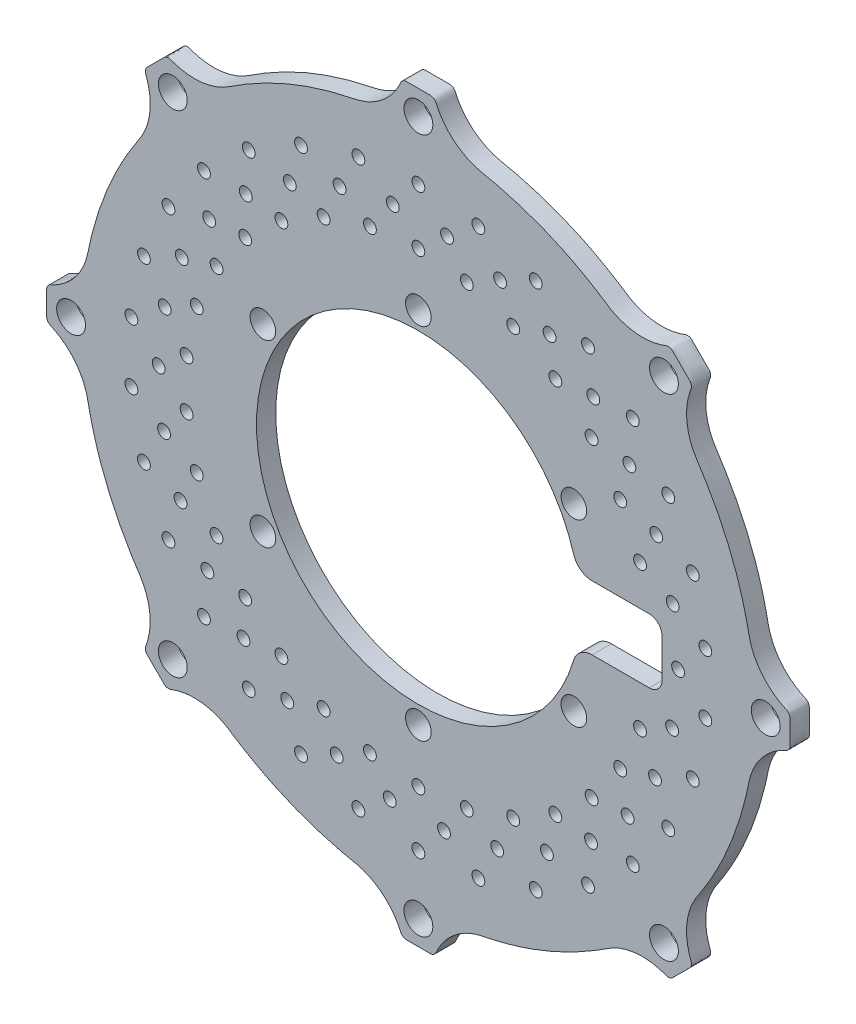
SolidWorks part; units mm, degrees
material "7075-T6, Plate (SS)"
ref_plane "Front Plane" through (0, 0, 0) normal (0, 0, 1) x (1, 0, 0)
ref_plane "Top Plane" through (0, 0, 0) normal (0, 1, 0) x (1, 0, 0)
ref_plane "Right Plane" through (0, 0, 0) normal (1, 0, 0) x (0, 0, -1)
sketch "Sketch1" plane through (0, 0, 0) normal (0, 0, 1) x (1, 0, 0)
  line L1 (-3.9972, 40.3023) -> (0, 28) construction
  line L3 (38, -3) -> (38, 3) construction
  line L4 (38, -3) -> (38, 3)
  line L5 (36, 5) -> (27.0936, 5)
  line L6 (36, -5) -> (27.0936, -5)
  line L7 (0, 0) -> (0, 48) construction
  line L8 (-2.8952, 57.0706) -> (-2.7624, 57.363)
  line L9 (-1.8466, 57.9614) -> (1.8466, 57.9614) construction
  line L10 (2.7624, 57.363) -> (2.7753, 57.3336)
  line L11 (-5, 52.2614) -> (5, 52.2614) construction
  line L12 (39.6791, 42.2906) -> (42.2906, 39.6791) construction
  line L13 (38.5785, 42.5034) -> (38.6085, 42.5151) construction
  line L14 (42.5151, 38.6085) -> (42.5034, 38.5785) construction
  line L15 (57.9614, 1.8466) -> (57.9614, -1.8466) construction
  line L16 (57.3336, 2.7753) -> (57.363, 2.7624) construction
  line L17 (57.363, -2.7624) -> (57.3336, -2.7753) construction
  line L18 (42.2906, -39.6791) -> (39.6791, -42.2906) construction
  line L19 (42.5034, -38.5785) -> (42.5151, -38.6085) construction
  line L20 (38.6085, -42.5151) -> (38.5785, -42.5034) construction
  line L21 (1.8466, -57.9614) -> (-1.8466, -57.9614) construction
  line L22 (2.7753, -57.3336) -> (2.7624, -57.363) construction
  line L23 (-2.7624, -57.363) -> (-2.7753, -57.3336) construction
  line L24 (-39.6791, -42.2906) -> (-42.2906, -39.6791) construction
  line L25 (-38.5785, -42.5034) -> (-38.6085, -42.5151) construction
  line L26 (-42.5151, -38.6085) -> (-42.5034, -38.5785) construction
  line L27 (-57.9614, -1.8466) -> (-57.9614, 1.8466) construction
  line L28 (-57.3336, -2.7753) -> (-57.363, -2.7624) construction
  line L29 (-57.363, 2.7624) -> (-57.3336, 2.7753) construction
  line L30 (-42.2906, 39.6791) -> (-39.6791, 42.2906) construction
  line L31 (-42.5034, 38.5785) -> (-42.5151, 38.6085) construction
  line L32 (-38.6085, 42.5151) -> (-38.5785, 42.5034) construction
  arc A0 (-10.0239, 51.5342) -> (-29.3522, 43.5281) centre (0, 0) ccw construction
  circle A1 centre (0, 0) radius 28 construction
  arc A3 (24.2164, 7.1504) -> (24.2164, -7.1504) centre (0, 0) ccw
  arc A4 (38, 3) -> (34, 3) centre (36, 3) ccw construction
  arc A5 (34, -3) -> (38, -3) centre (36, -3) ccw construction
  arc A6 (36, -5) -> (38, -3) centre (36, -3) ccw
  arc A7 (38, 3) -> (36, 5) centre (36, 3) ccw
  arc A8 (27.0936, -5) -> (24.2164, -7.1504) centre (27.0936, -8) ccw
  arc A9 (27.0936, 5) -> (24.2164, 7.1504) centre (27.0936, 8) cw
  circle A10 centre (0, 0) radius 36.3456 construction
  circle A11 centre (0, 36.3456) radius 1
  circle A12 centre (0, 45) radius 1
  arc A13 (45, 0) -> (-45, 0) centre (0, 0) ccw construction
  circle A14 centre (9.356, 44.0166) radius 1
  circle A15 centre (7.5567, 35.5513) radius 1
  circle A16 centre (18.3031, 41.1095) radius 1
  circle A17 centre (14.7831, 33.2033) radius 1
  circle A18 centre (26.4503, 36.4058) radius 1
  circle A19 centre (21.3634, 29.4042) radius 1
  circle A20 centre (33.4415, 30.1109) radius 1
  circle A21 centre (27.01, 24.3199) radius 1
  circle A22 centre (38.9711, 22.5) radius 1
  circle A23 centre (31.4762, 18.1728) radius 1
  circle A24 centre (42.7975, 13.9058) radius 1
  circle A25 centre (34.5667, 11.2314) radius 1
  circle A26 centre (44.7535, 4.7038) radius 1
  circle A27 centre (36.1465, 3.7991) radius 1
  circle A28 centre (44.7535, -4.7038) radius 1
  circle A29 centre (36.1465, -3.7991) radius 1
  circle A30 centre (42.7975, -13.9058) radius 1
  circle A31 centre (34.5667, -11.2314) radius 1
  circle A32 centre (38.9711, -22.5) radius 1
  circle A33 centre (31.4762, -18.1728) radius 1
  circle A34 centre (33.4415, -30.1109) radius 1
  circle A35 centre (27.01, -24.3199) radius 1
  circle A36 centre (26.4503, -36.4058) radius 1
  circle A37 centre (21.3634, -29.4042) radius 1
  circle A38 centre (18.3031, -41.1095) radius 1
  circle A39 centre (14.7831, -33.2033) radius 1
  circle A40 centre (9.356, -44.0166) radius 1
  circle A41 centre (7.5567, -35.5513) radius 1
  circle A42 centre (0, -45) radius 1
  circle A43 centre (0, -36.3456) radius 1
  circle A44 centre (-9.356, -44.0166) radius 1
  circle A45 centre (-7.5567, -35.5513) radius 1
  circle A46 centre (-18.3031, -41.1095) radius 1
  circle A47 centre (-14.7831, -33.2033) radius 1
  circle A48 centre (-26.4503, -36.4058) radius 1
  circle A49 centre (-21.3634, -29.4042) radius 1
  circle A50 centre (-33.4415, -30.1109) radius 1
  circle A51 centre (-27.01, -24.3199) radius 1
  circle A52 centre (-38.9711, -22.5) radius 1
  circle A53 centre (-31.4762, -18.1728) radius 1
  circle A54 centre (-42.7975, -13.9058) radius 1
  circle A55 centre (-34.5667, -11.2314) radius 1
  circle A56 centre (-44.7535, -4.7038) radius 1
  circle A57 centre (-36.1465, -3.7991) radius 1
  circle A58 centre (-44.7535, 4.7038) radius 1
  circle A59 centre (-36.1465, 3.7991) radius 1
  circle A60 centre (-42.7975, 13.9058) radius 1
  circle A61 centre (-34.5667, 11.2314) radius 1
  circle A62 centre (-38.9711, 22.5) radius 1
  circle A63 centre (-31.4762, 18.1728) radius 1
  circle A64 centre (-33.4415, 30.1109) radius 1
  circle A65 centre (-27.01, 24.3199) radius 1
  circle A66 centre (-26.4503, 36.4058) radius 1
  circle A67 centre (-21.3634, 29.4042) radius 1
  circle A68 centre (-18.3031, 41.1095) radius 1
  circle A69 centre (-14.7831, 33.2033) radius 1
  circle A70 centre (-9.356, 44.0166) radius 1
  circle A71 centre (-7.5567, 35.5513) radius 1
  circle A72 centre (0, 0) radius 40.5 construction
  circle A73 centre (-3.9972, 40.3023) radius 1
  circle A74 centre (4.4694, 40.2526) radius 1
  circle A75 centre (12.7407, 38.4438) radius 1
  circle A76 centre (20.4552, 34.9547) radius 1
  circle A77 centre (27.2757, 29.938) radius 1
  circle A78 centre (32.9042, 23.6128) radius 1
  circle A79 centre (37.0945, 16.2557) radius 1
  circle A80 centre (39.6637, 8.1881) radius 1
  circle A81 centre (40.4993, -0.2374) radius 1
  circle A82 centre (39.5649, -8.6525) radius 1
  circle A83 centre (36.9014, -16.6894) radius 1
  circle A84 centre (32.6251, -23.9969) radius 1
  circle A85 centre (26.9229, -30.2557) radius 1
  circle A86 centre (20.0441, -35.1921) radius 1
  circle A87 centre (12.2892, -38.5905) radius 1
  circle A88 centre (3.9972, -40.3023) radius 1
  circle A89 centre (-4.4694, -40.2526) radius 1
  circle A90 centre (-12.7407, -38.4438) radius 1
  circle A91 centre (-20.4552, -34.9547) radius 1
  circle A92 centre (-27.2757, -29.938) radius 1
  circle A93 centre (-32.9042, -23.6128) radius 1
  circle A94 centre (-37.0945, -16.2557) radius 1
  circle A95 centre (-39.6637, -8.1881) radius 1
  circle A96 centre (-40.4993, 0.2374) radius 1
  circle A97 centre (-39.5649, 8.6525) radius 1
  circle A98 centre (-36.9014, 16.6894) radius 1
  circle A99 centre (-32.6251, 23.9969) radius 1
  circle A100 centre (-26.9229, 30.2557) radius 1
  circle A101 centre (-20.0441, 35.1921) radius 1
  circle A102 centre (-12.2892, 38.5905) radius 1
  arc A104 (-2.8952, 57.0706) -> (-10.0239, 51.5342) centre (-11.9332, 61.3502) cw construction
  arc A105 (2.7753, 57.3336) -> (10.0239, 51.5342) centre (11.9332, 61.3502) ccw construction
  arc A106 (38.5785, 42.5034) -> (29.3522, 43.5281) centre (34.9431, 51.8192) cw construction
  arc A107 (42.5034, 38.5785) -> (43.5281, 29.3522) centre (51.8192, 34.9431) ccw construction
  arc A108 (57.3336, 2.7753) -> (51.5342, 10.0239) centre (61.3502, 11.9332) cw construction
  arc A109 (57.3336, -2.7753) -> (51.5342, -10.0239) centre (61.3502, -11.9332) ccw construction
  arc A110 (42.5034, -38.5785) -> (43.5281, -29.3522) centre (51.8192, -34.9431) cw construction
  arc A111 (38.5785, -42.5034) -> (29.3522, -43.5281) centre (34.9431, -51.8192) ccw construction
  arc A112 (2.7753, -57.3336) -> (10.0239, -51.5342) centre (11.9332, -61.3502) cw construction
  arc A113 (-2.7753, -57.3336) -> (-10.0239, -51.5342) centre (-11.9332, -61.3502) ccw construction
  arc A114 (-38.5785, -42.5034) -> (-29.3522, -43.5281) centre (-34.9431, -51.8192) cw construction
  arc A115 (-42.5034, -38.5785) -> (-43.5281, -29.3522) centre (-51.8192, -34.9431) ccw construction
  arc A116 (-57.3336, -2.7753) -> (-51.5342, -10.0239) centre (-61.3502, -11.9332) cw construction
  arc A117 (-57.3336, 2.7753) -> (-51.5342, 10.0239) centre (-61.3502, 11.9332) ccw construction
  arc A118 (-42.5034, 38.5785) -> (-43.5281, 29.3522) centre (-51.8192, 34.9431) cw construction
  arc A119 (-38.5785, 42.5034) -> (-29.3522, 43.5281) centre (-34.9431, 51.8192) ccw construction
  arc A120 (29.3522, 43.5281) -> (10.0239, 51.5342) centre (0, 0) ccw construction
  arc A121 (51.5342, 10.0239) -> (43.5281, 29.3522) centre (0, 0) ccw construction
  arc A122 (10.0239, -51.5342) -> (29.3522, -43.5281) centre (0, 0) ccw construction
  arc A123 (43.5281, -29.3522) -> (51.5342, -10.0239) centre (0, 0) ccw construction
  arc A124 (-29.3522, -43.5281) -> (-10.0239, -51.5342) centre (0, 0) ccw construction
  arc A125 (-51.5342, -10.0239) -> (-43.5281, -29.3522) centre (0, 0) ccw construction
  arc A126 (-43.5281, 29.3522) -> (-51.5342, 10.0239) centre (0, 0) ccw construction
  arc A127 (1.8466, 57.9614) -> (2.7624, 57.363) centre (1.8466, 56.9614) cw construction
  arc A128 (-2.7624, 57.363) -> (-1.8466, 57.9614) centre (-1.8466, 56.9614) cw construction
  arc A129 (-42.2906, 39.6791) -> (-42.5151, 38.6085) centre (-41.5835, 38.972) ccw construction
  arc A130 (-39.6791, 42.2906) -> (-38.6085, 42.5151) centre (-38.972, 41.5835) cw construction
  arc A131 (-57.9614, 1.8466) -> (-57.363, 2.7624) centre (-56.9614, 1.8466) cw construction
  arc A132 (-57.9614, -1.8466) -> (-57.363, -2.7624) centre (-56.9614, -1.8466) ccw construction
  arc A133 (-42.2906, -39.6791) -> (-42.5151, -38.6085) centre (-41.5835, -38.972) cw construction
  arc A134 (-39.6791, -42.2906) -> (-38.6085, -42.5151) centre (-38.972, -41.5835) ccw construction
  arc A135 (-1.8466, -57.9614) -> (-2.7624, -57.363) centre (-1.8466, -56.9614) cw construction
  arc A136 (1.8466, -57.9614) -> (2.7624, -57.363) centre (1.8466, -56.9614) ccw construction
  arc A137 (42.2906, -39.6791) -> (42.5151, -38.6085) centre (41.5835, -38.972) ccw construction
  arc A138 (39.6791, -42.2906) -> (38.6085, -42.5151) centre (38.972, -41.5835) cw construction
  arc A139 (57.9614, -1.8466) -> (57.363, -2.7624) centre (56.9614, -1.8466) cw construction
  arc A140 (57.9614, 1.8466) -> (57.363, 2.7624) centre (56.9614, 1.8466) ccw construction
  arc A141 (42.2906, 39.6791) -> (42.5151, 38.6085) centre (41.5835, 38.972) cw construction
  arc A142 (39.6791, 42.2906) -> (38.6085, 42.5151) centre (38.972, 41.5835) ccw construction
  spline S0 degree 3 poles (-2.8952, 57.0706) (-3.9074, 54.9332) (-5.5869, 53.2683) (-7.7332, 52.275) (-8.2182, 52.0505) (-9.2243, 51.6793) (-10.8147, 51.3824) (-11.8574, 51.1462) (-12.3768, 51.0202) (-17.6601, 49.7386) (-22.6829, 47.6581) (-27.3251, 44.8285) (-27.7814, 44.5503) (-28.6857, 43.98) (-30.0203, 43.0653) (-30.9941, 42.6164) (-31.4958, 42.4322) (-33.8095, 41.5825) (-36.2742, 41.6063) (-38.571, 42.5005) (-38.5718, 42.5008) (-38.5735, 42.5015) (-38.576, 42.5025) (-38.5777, 42.5031) (-38.5785, 42.5034) (-38.5793, 42.5038) (-38.581, 42.5044) (-38.5835, 42.5054) (-38.5852, 42.506) (-38.586, 42.5064) (-38.591, 42.5083) (-38.596, 42.5102) (-38.601, 42.5122) (-38.6018, 42.5125) (-38.6035, 42.5132) (-38.606, 42.5141) (-38.6076, 42.5148) (-38.6085, 42.5151) (-38.6093, 42.5154) (-38.611, 42.5161) (-38.6135, 42.5171) (-38.6151, 42.5177) (-38.616, 42.518) (-38.8925, 42.6234) (-39.1877, 42.6038) (-39.4479, 42.463) (-39.4761, 42.4478) (-39.531, 42.4146) (-39.6111, 42.3586) (-39.6564, 42.3133) (-39.6791, 42.2906) (-39.7018, 42.268) (-39.7471, 42.2227) (-39.815, 42.1547) (-39.8603, 42.1094) (-39.883, 42.0867) (-40.6176, 41.3522) (-41.3522, 40.6176) (-42.0867, 39.883) (-42.1094, 39.8603) (-42.1547, 39.815) (-42.2227, 39.7471) (-42.268, 39.7018) (-42.2906, 39.6791) (-42.3133, 39.6564) (-42.3586, 39.6111) (-42.4146, 39.531) (-42.4478, 39.4761) (-42.463, 39.4479) (-42.6038, 39.1877) (-42.6234, 38.8925) (-42.518, 38.616) (-42.5177, 38.6151) (-42.5171, 38.6135) (-42.5161, 38.611) (-42.5154, 38.6093) (-42.5151, 38.6085) (-42.5148, 38.6076) (-42.5141, 38.606) (-42.5132, 38.6035) (-42.5125, 38.6018) (-42.5122, 38.601) (-42.5102, 38.596) (-42.5083, 38.591) (-42.5064, 38.586) (-42.506, 38.5852) (-42.5054, 38.5835) (-42.5044, 38.581) (-42.5038, 38.5793) (-42.5034, 38.5785) (-42.5031, 38.5777) (-42.5025, 38.576) (-42.5015, 38.5735) (-42.5008, 38.5718) (-42.5005, 38.571) (-41.6063, 36.2742) (-41.5825, 33.8095) (-42.4322, 31.4958) (-42.6164, 30.9941) (-43.0653, 30.0203) (-43.98, 28.6857) (-44.5503, 27.7814) (-44.8285, 27.3251) (-47.6581, 22.6829) (-49.7386, 17.6601) (-51.0202, 12.3768) (-51.1462, 11.8574) (-51.3824, 10.8147) (-51.6793, 9.2243) (-52.0505, 8.2182) (-52.275, 7.7332) (-53.3102, 5.4963) (-55.0698, 3.7704) (-57.3262, 2.7786) (-57.327, 2.7782) (-57.3287, 2.7775) (-57.3311, 2.7764) (-57.3328, 2.7757) (-57.3336, 2.7753) (-57.3344, 2.775) (-57.336, 2.7743) (-57.3385, 2.7732) (-57.3401, 2.7725) (-57.341, 2.7721) (-57.3459, 2.77) (-57.3508, 2.7678) (-57.3557, 2.7657) (-57.3565, 2.7653) (-57.3581, 2.7646) (-57.3606, 2.7635) (-57.3622, 2.7628) (-57.363, 2.7624) (-57.3638, 2.7621) (-57.3655, 2.7613) (-57.3679, 2.7603) (-57.3696, 2.7595) (-57.3704, 2.7592) (-57.6404, 2.6381) (-57.8354, 2.4156) (-57.9198, 2.132) (-57.9289, 2.1013) (-57.9443, 2.039) (-57.9614, 1.9428) (-57.9614, 1.8787) (-57.9614, 1.8466) (-57.9614, 1.8146) (-57.9614, 1.7505) (-57.9614, 1.6544) (-57.9614, 1.5903) (-57.9614, 1.5583) (-57.9614, 0.5194) (-57.9614, -0.5194) (-57.9614, -1.5583) (-57.9614, -1.5903) (-57.9614, -1.6544) (-57.9614, -1.7505) (-57.9614, -1.8146) (-57.9614, -1.8466) (-57.9614, -1.8787) (-57.9614, -1.9428) (-57.9443, -2.039) (-57.9289, -2.1013) (-57.9198, -2.132) (-57.8354, -2.4156) (-57.6404, -2.6381) (-57.3704, -2.7592) (-57.3696, -2.7595) (-57.3679, -2.7603) (-57.3655, -2.7613) (-57.3638, -2.7621) (-57.363, -2.7624) (-57.3622, -2.7628) (-57.3606, -2.7635) (-57.3581, -2.7646) (-57.3565, -2.7653) (-57.3557, -2.7657) (-57.3508, -2.7678) (-57.3459, -2.77) (-57.341, -2.7721) (-57.3401, -2.7725) (-57.3385, -2.7732) (-57.336, -2.7743) (-57.3344, -2.775) (-57.3336, -2.7753) (-57.3328, -2.7757) (-57.3311, -2.7764) (-57.3287, -2.7775) (-57.327, -2.7782) (-57.3262, -2.7786) (-55.0698, -3.7704) (-53.3102, -5.4963) (-52.275, -7.7332) (-52.0505, -8.2182) (-51.6793, -9.2243) (-51.3824, -10.8147) (-51.1462, -11.8574) (-51.0202, -12.3768) (-49.7386, -17.6601) (-47.6581, -22.6829) (-44.8285, -27.3251) (-44.5503, -27.7814) (-43.98, -28.6857) (-43.0653, -30.0203) (-42.6164, -30.9941) (-42.4322, -31.4958) (-41.5825, -33.8095) (-41.6063, -36.2742) (-42.5005, -38.571) (-42.5008, -38.5718) (-42.5015, -38.5735) (-42.5025, -38.576) (-42.5031, -38.5777) (-42.5034, -38.5785) (-42.5038, -38.5793) (-42.5044, -38.581) (-42.5054, -38.5835) (-42.506, -38.5852) (-42.5064, -38.586) (-42.5083, -38.591) (-42.5102, -38.596) (-42.5122, -38.601) (-42.5125, -38.6018) (-42.5132, -38.6035) (-42.5141, -38.606) (-42.5148, -38.6076) (-42.5151, -38.6085) (-42.5154, -38.6093) (-42.5161, -38.611) (-42.5171, -38.6135) (-42.5177, -38.6151) (-42.518, -38.616) (-42.6234, -38.8925) (-42.6038, -39.1877) (-42.463, -39.4479) (-42.4478, -39.4761) (-42.4146, -39.531) (-42.3586, -39.6111) (-42.3133, -39.6564) (-42.2906, -39.6791) (-42.268, -39.7018) (-42.2227, -39.7471) (-42.1547, -39.815) (-42.1094, -39.8603) (-42.0867, -39.883) (-41.3522, -40.6176) (-40.6176, -41.3522) (-39.883, -42.0867) (-39.8603, -42.1094) (-39.815, -42.1547) (-39.7471, -42.2227) (-39.7018, -42.268) (-39.6791, -42.2906) (-39.6564, -42.3133) (-39.6111, -42.3586) (-39.531, -42.4146) (-39.4761, -42.4478) (-39.4479, -42.463) (-39.1877, -42.6038) (-38.8925, -42.6234) (-38.616, -42.518) (-38.6151, -42.5177) (-38.6135, -42.5171) (-38.611, -42.5161) (-38.6093, -42.5154) (-38.6085, -42.5151) (-38.6076, -42.5148) (-38.606, -42.5141) (-38.6035, -42.5132) (-38.6018, -42.5125) (-38.601, -42.5122) (-38.596, -42.5102) (-38.591, -42.5083) (-38.586, -42.5064) (-38.5852, -42.506) (-38.5835, -42.5054) (-38.581, -42.5044) (-38.5793, -42.5038) (-38.5785, -42.5034) (-38.5777, -42.5031) (-38.576, -42.5025) (-38.5735, -42.5015) (-38.5718, -42.5008) (-38.571, -42.5005) (-36.2742, -41.6063) (-33.8095, -41.5825) (-31.4958, -42.4322) (-30.9941, -42.6164) (-30.0203, -43.0653) (-28.6857, -43.98) (-27.7814, -44.5503) (-27.3251, -44.8285) (-22.6829, -47.6581) (-17.6601, -49.7386) (-12.3768, -51.0202) (-11.8574, -51.1462) (-10.8147, -51.3824) (-9.2243, -51.6793) (-8.2182, -52.0505) (-7.7332, -52.275) (-5.4963, -53.3102) (-3.7704, -55.0698) (-2.7786, -57.3262) (-2.7782, -57.327) (-2.7775, -57.3287) (-2.7764, -57.3311) (-2.7757, -57.3328) (-2.7753, -57.3336) (-2.775, -57.3344) (-2.7743, -57.336) (-2.7732, -57.3385) (-2.7725, -57.3401) (-2.7721, -57.341) (-2.77, -57.3459) (-2.7678, -57.3508) (-2.7657, -57.3557) (-2.7653, -57.3565) (-2.7646, -57.3581) (-2.7635, -57.3606) (-2.7628, -57.3622) (-2.7624, -57.363) (-2.7621, -57.3638) (-2.7613, -57.3655) (-2.7603, -57.3679) (-2.7595, -57.3696) (-2.7592, -57.3704) (-2.6381, -57.6404) (-2.4156, -57.8354) (-2.132, -57.9198) (-2.1013, -57.9289) (-2.039, -57.9443) (-1.9428, -57.9614) (-1.8787, -57.9614) (-1.8466, -57.9614) (-1.8146, -57.9614) (-1.7505, -57.9614) (-1.6544, -57.9614) (-1.5903, -57.9614) (-1.5583, -57.9614) (-0.5194, -57.9614) (0.5194, -57.9614) (1.5583, -57.9614) (1.5903, -57.9614) (1.6544, -57.9614) (1.7505, -57.9614) (1.8146, -57.9614) (1.8466, -57.9614) (1.8787, -57.9614) (1.9428, -57.9614) (2.039, -57.9443) (2.1013, -57.9289) (2.132, -57.9198) (2.4156, -57.8354) (2.6381, -57.6404) (2.7592, -57.3704) (2.7595, -57.3696) (2.7603, -57.3679) (2.7613, -57.3655) (2.7621, -57.3638) (2.7624, -57.363) (2.7628, -57.3622) (2.7635, -57.3606) (2.7646, -57.3581) (2.7653, -57.3565) (2.7657, -57.3557) (2.7678, -57.3508) (2.77, -57.3459) (2.7721, -57.341) (2.7725, -57.3401) (2.7732, -57.3385) (2.7743, -57.336) (2.775, -57.3344) (2.7753, -57.3336) (2.7757, -57.3328) (2.7764, -57.3311) (2.7775, -57.3287) (2.7782, -57.327) (2.7786, -57.3262) (3.7704, -55.0698) (5.4963, -53.3102) (7.7332, -52.275) (8.2182, -52.0505) (9.2243, -51.6793) (10.8147, -51.3824) (11.8574, -51.1462) (12.3768, -51.0202) (17.6601, -49.7386) (22.6829, -47.6581) (27.3251, -44.8285) (27.7814, -44.5503) (28.6857, -43.98) (30.0203, -43.0653) (30.9941, -42.6164) (31.4958, -42.4322) (33.8095, -41.5825) (36.2742, -41.6063) (38.571, -42.5005) (38.5718, -42.5008) (38.5735, -42.5015) (38.576, -42.5025) (38.5777, -42.5031) (38.5785, -42.5034) (38.5793, -42.5038) (38.581, -42.5044) (38.5835, -42.5054) (38.5852, -42.506) (38.586, -42.5064) (38.591, -42.5083) (38.596, -42.5102) (38.601, -42.5122) (38.6018, -42.5125) (38.6035, -42.5132) (38.606, -42.5141) (38.6076, -42.5148) (38.6085, -42.5151) (38.6093, -42.5154) (38.611, -42.5161) (38.6135, -42.5171) (38.6151, -42.5177) (38.616, -42.518) (38.8925, -42.6234) (39.1877, -42.6038) (39.4479, -42.463) (39.4761, -42.4478) (39.531, -42.4146) (39.6111, -42.3586) (39.6564, -42.3133) (39.6791, -42.2906) (39.7018, -42.268) (39.7471, -42.2227) (39.815, -42.1547) (39.8603, -42.1094) (39.883, -42.0867) (40.6176, -41.3522) (41.3522, -40.6176) (42.0867, -39.883) (42.1094, -39.8603) (42.1547, -39.815) (42.2227, -39.7471) (42.268, -39.7018) (42.2906, -39.6791) (42.3133, -39.6564) (42.3586, -39.6111) (42.4146, -39.531) (42.4478, -39.4761) (42.463, -39.4479) (42.6038, -39.1877) (42.6234, -38.8925) (42.518, -38.616) (42.5177, -38.6151) (42.5171, -38.6135) (42.5161, -38.611) (42.5154, -38.6093) (42.5151, -38.6085) (42.5148, -38.6076) (42.5141, -38.606) (42.5132, -38.6035) (42.5125, -38.6018) (42.5122, -38.601) (42.5102, -38.596) (42.5083, -38.591) (42.5064, -38.586) (42.506, -38.5852) (42.5054, -38.5835) (42.5044, -38.581) (42.5038, -38.5793) (42.5034, -38.5785) (42.5031, -38.5777) (42.5025, -38.576) (42.5015, -38.5735) (42.5008, -38.5718) (42.5005, -38.571) (41.6063, -36.2742) (41.5825, -33.8095) (42.4322, -31.4958) (42.6164, -30.9941) (43.0653, -30.0203) (43.98, -28.6857) (44.5503, -27.7814) (44.8285, -27.3251) (47.6581, -22.6829) (49.7386, -17.6601) (51.0202, -12.3768) (51.1462, -11.8574) (51.3824, -10.8147) (51.6793, -9.2243) (52.0505, -8.2182) (52.275, -7.7332) (53.3102, -5.4963) (55.0698, -3.7704) (57.3262, -2.7786) (57.327, -2.7782) (57.3287, -2.7775) (57.3311, -2.7764) (57.3328, -2.7757) (57.3336, -2.7753) (57.3344, -2.775) (57.336, -2.7743) (57.3385, -2.7732) (57.3401, -2.7725) (57.341, -2.7721) (57.3459, -2.77) (57.3508, -2.7678) (57.3557, -2.7657) (57.3565, -2.7653) (57.3581, -2.7646) (57.3606, -2.7635) (57.3622, -2.7628) (57.363, -2.7624) (57.3638, -2.7621) (57.3655, -2.7613) (57.3679, -2.7603) (57.3696, -2.7595) (57.3704, -2.7592) (57.6404, -2.6381) (57.8354, -2.4156) (57.9198, -2.132) (57.9289, -2.1013) (57.9443, -2.039) (57.9614, -1.9428) (57.9614, -1.8787) (57.9614, -1.8466) (57.9614, -1.8146) (57.9614, -1.7505) (57.9614, -1.6544) (57.9614, -1.5903) (57.9614, -1.5583) (57.9614, -0.5194) (57.9614, 0.5194) (57.9614, 1.5583) (57.9614, 1.5903) (57.9614, 1.6544) (57.9614, 1.7505) (57.9614, 1.8146) (57.9614, 1.8466) (57.9614, 1.8787) (57.9614, 1.9428) (57.9443, 2.039) (57.9289, 2.1013) (57.9198, 2.132) (57.8354, 2.4156) (57.6404, 2.6381) (57.3704, 2.7592) (57.3696, 2.7595) (57.3679, 2.7603) (57.3655, 2.7613) (57.3638, 2.7621) (57.363, 2.7624) (57.3622, 2.7628) (57.3606, 2.7635) (57.3581, 2.7646) (57.3565, 2.7653) (57.3557, 2.7657) (57.3508, 2.7678) (57.3459, 2.77) (57.341, 2.7721) (57.3401, 2.7725) (57.3385, 2.7732) (57.336, 2.7743) (57.3344, 2.775) (57.3336, 2.7753) (57.3328, 2.7757) (57.3311, 2.7764) (57.3287, 2.7775) (57.327, 2.7782) (57.3262, 2.7786) (55.0698, 3.7704) (53.3102, 5.4963) (52.275, 7.7332) (52.0505, 8.2182) (51.6793, 9.2243) (51.3824, 10.8147) (51.1462, 11.8574) (51.0202, 12.3768) (49.7386, 17.6601) (47.6581, 22.6829) (44.8285, 27.3251) (44.5503, 27.7814) (43.98, 28.6857) (43.0653, 30.0203) (42.6164, 30.9941) (42.4322, 31.4958) (41.5825, 33.8095) (41.6063, 36.2742) (42.5005, 38.571) (42.5008, 38.5718) (42.5015, 38.5735) (42.5025, 38.576) (42.5031, 38.5777) (42.5034, 38.5785) (42.5038, 38.5793) (42.5044, 38.581) (42.5054, 38.5835) (42.506, 38.5852) (42.5064, 38.586) (42.5083, 38.591) (42.5102, 38.596) (42.5122, 38.601) (42.5125, 38.6018) (42.5132, 38.6035) (42.5141, 38.606) (42.5148, 38.6076) (42.5151, 38.6085) (42.5154, 38.6093) (42.5161, 38.611) (42.5171, 38.6135) (42.5177, 38.6151) (42.518, 38.616) (42.6234, 38.8925) (42.6038, 39.1877) (42.463, 39.4479) (42.4478, 39.4761) (42.4146, 39.531) (42.3586, 39.6111) (42.3133, 39.6564) (42.2906, 39.6791) (42.268, 39.7018) (42.2227, 39.7471) (42.1547, 39.815) (42.1094, 39.8603) (42.0867, 39.883) (41.3522, 40.6176) (40.6176, 41.3522) (39.883, 42.0867) (39.8603, 42.1094) (39.815, 42.1547) (39.7471, 42.2227) (39.7018, 42.268) (39.6791, 42.2906) (39.6564, 42.3133) (39.6111, 42.3586) (39.531, 42.4146) (39.4761, 42.4478) (39.4479, 42.463) (39.1877, 42.6038) (38.8925, 42.6234) (38.616, 42.518) (38.6151, 42.5177) (38.6135, 42.5171) (38.611, 42.5161) (38.6093, 42.5154) (38.6085, 42.5151) (38.6076, 42.5148) (38.606, 42.5141) (38.6035, 42.5132) (38.6018, 42.5125) (38.601, 42.5122) (38.596, 42.5102) (38.591, 42.5083) (38.586, 42.5064) (38.5852, 42.506) (38.5835, 42.5054) (38.581, 42.5044) (38.5793, 42.5038) (38.5785, 42.5034) (38.5777, 42.5031) (38.576, 42.5025) (38.5735, 42.5015) (38.5718, 42.5008) (38.571, 42.5005) (36.2742, 41.6063) (33.8095, 41.5825) (31.4958, 42.4322) (30.9941, 42.6164) (30.0203, 43.0653) (28.6857, 43.98) (27.7814, 44.5503) (27.3251, 44.8285) (22.6829, 47.6581) (17.6601, 49.7386) (12.3768, 51.0202) (11.8574, 51.1462) (10.8147, 51.3824) (9.2243, 51.6793) (8.2182, 52.0505) (7.7332, 52.275) (5.5869, 53.2683) (3.9074, 54.9332) (2.8952, 57.0706) (2.8663, 57.1317) (2.8097, 57.2544) (2.7303, 57.4441) (2.6534, 57.5561) (2.6097, 57.6076) (2.4833, 57.7569) (2.3195, 57.864) (2.132, 57.9198) (2.1013, 57.9289) (2.039, 57.9443) (1.9428, 57.9614) (1.8787, 57.9614) (1.8466, 57.9614) (1.8146, 57.9614) (1.7505, 57.9614) (1.6544, 57.9614) (1.5903, 57.9614) (1.5583, 57.9614) (0.5194, 57.9614) (-0.5194, 57.9614) (-1.5583, 57.9614) (-1.5903, 57.9614) (-1.6544, 57.9614) (-1.7505, 57.9614) (-1.8146, 57.9614) (-1.8466, 57.9614) (-1.8787, 57.9614) (-1.9428, 57.9614) (-2.039, 57.9443) (-2.1013, 57.9289) (-2.132, 57.9198) (-2.3195, 57.864) (-2.4833, 57.7569) (-2.6097, 57.6076) (-2.6534, 57.5561) (-2.7303, 57.4441) (-2.8097, 57.2544) (-2.8663, 57.1317) (-2.8952, 57.0706) (-3.9074, 54.9332) (-5.5869, 53.2683) knots -0.000551 0 0 0 0.018513 0.018513 0.018513 0.022871 0.027229 0.031586 0.031586 0.031586 0.07556 0.07556 0.07556 0.079917 0.084275 0.088632 0.088632 0.088632 0.107862 0.107862 0.107862 0.107869 0.107877 0.107884 0.107884 0.107884 0.107891 0.107898 0.107906 0.107906 0.107906 0.107949 0.107949 0.107949 0.107957 0.107964 0.107971 0.107971 0.107971 0.107979 0.107986 0.107993 0.107993 0.107993 0.110259 0.110259 0.110259 0.11052 0.110782 0.111043 0.111043 0.111043 0.111304 0.111565 0.111827 0.111827 0.111827 0.120297 0.120297 0.120297 0.120558 0.120819 0.12108 0.12108 0.12108 0.121342 0.121603 0.121864 0.121864 0.121864 0.12413 0.12413 0.12413 0.124137 0.124145 0.124152 0.124152 0.124152 0.124159 0.124166 0.124174 0.124174 0.124174 0.124217 0.124217 0.124217 0.124225 0.124232 0.124239 0.124239 0.124239 0.124247 0.124254 0.124261 0.124261 0.124261 0.143491 0.143491 0.143491 0.147848 0.152206 0.156564 0.156564 0.156564 0.200537 0.200537 0.200537 0.204894 0.209252 0.21361 0.21361 0.21361 0.232839 0.232839 0.232839 0.232847 0.232854 0.232861 0.232861 0.232861 0.232868 0.232876 0.232883 0.232883 0.232883 0.232927 0.232927 0.232927 0.232934 0.232941 0.232949 0.232949 0.232949 0.232956 0.232963 0.23297 0.23297 0.23297 0.235236 0.235236 0.235236 0.235498 0.235759 0.23602 0.23602 0.23602 0.236281 0.236543 0.236804 0.236804 0.236804 0.245274 0.245274 0.245274 0.245535 0.245796 0.246058 0.246058 0.246058 0.246319 0.24658 0.246841 0.246841 0.246841 0.249107 0.249107 0.249107 0.249115 0.249122 0.249129 0.249129 0.249129 0.249137 0.249144 0.249151 0.249151 0.249151 0.249195 0.249195 0.249195 0.249202 0.249209 0.249217 0.249217 0.249217 0.249224 0.249231 0.249238 0.249238 0.249238 0.268468 0.268468 0.268468 0.272826 0.277183 0.281541 0.281541 0.281541 0.325514 0.325514 0.325514 0.329872 0.334229 0.338587 0.338587 0.338587 0.357817 0.357817 0.357817 0.357824 0.357831 0.357839 0.357839 0.357839 0.357846 0.357853 0.35786 0.35786 0.35786 0.357904 0.357904 0.357904 0.357911 0.357919 0.357926 0.357926 0.357926 0.357933 0.35794 0.357948 0.357948 0.357948 0.360214 0.360214 0.360214 0.360475 0.360736 0.360997 0.360997 0.360997 0.361259 0.36152 0.361781 0.361781 0.361781 0.370251 0.370251 0.370251 0.370513 0.370774 0.371035 0.371035 0.371035 0.371296 0.371557 0.371819 0.371819 0.371819 0.374085 0.374085 0.374085 0.374092 0.374099 0.374107 0.374107 0.374107 0.374114 0.374121 0.374128 0.374128 0.374128 0.374172 0.374172 0.374172 0.374179 0.374187 0.374194 0.374194 0.374194 0.374201 0.374209 0.374216 0.374216 0.374216 0.393445 0.393445 0.393445 0.397803 0.402161 0.406518 0.406518 0.406518 0.450492 0.450492 0.450492 0.454849 0.459207 0.463564 0.463564 0.463564 0.482794 0.482794 0.482794 0.482801 0.482809 0.482816 0.482816 0.482816 0.482823 0.48283 0.482838 0.482838 0.482838 0.482881 0.482881 0.482881 0.482889 0.482896 0.482903 0.482903 0.482903 0.482911 0.482918 0.482925 0.482925 0.482925 0.485191 0.485191 0.485191 0.485452 0.485714 0.485975 0.485975 0.485975 0.486236 0.486497 0.486759 0.486759 0.486759 0.495229 0.495229 0.495229 0.49549 0.495751 0.496012 0.496012 0.496012 0.496274 0.496535 0.496796 0.496796 0.496796 0.499062 0.499062 0.499062 0.499069 0.499077 0.499084 0.499084 0.499084 0.499091 0.499098 0.499106 0.499106 0.499106 0.499149 0.499149 0.499149 0.499157 0.499164 0.499171 0.499171 0.499171 0.499179 0.499186 0.499193 0.499193 0.499193 0.518423 0.518423 0.518423 0.52278 0.527138 0.531496 0.531496 0.531496 0.575469 0.575469 0.575469 0.579826 0.584184 0.588542 0.588542 0.588542 0.607771 0.607771 0.607771 0.607779 0.607786 0.607793 0.607793 0.607793 0.6078 0.607808 0.607815 0.607815 0.607815 0.607859 0.607859 0.607859 0.607866 0.607873 0.607881 0.607881 0.607881 0.607888 0.607895 0.607902 0.607902 0.607902 0.610168 0.610168 0.610168 0.61043 0.610691 0.610952 0.610952 0.610952 0.611213 0.611475 0.611736 0.611736 0.611736 0.620206 0.620206 0.620206 0.620467 0.620728 0.62099 0.62099 0.62099 0.621251 0.621512 0.621773 0.621773 0.621773 0.624039 0.624039 0.624039 0.624047 0.624054 0.624061 0.624061 0.624061 0.624069 0.624076 0.624083 0.624083 0.624083 0.624127 0.624127 0.624127 0.624134 0.624141 0.624149 0.624149 0.624149 0.624156 0.624163 0.62417 0.62417 0.62417 0.6434 0.6434 0.6434 0.647758 0.652115 0.656473 0.656473 0.656473 0.700446 0.700446 0.700446 0.704804 0.709161 0.713519 0.713519 0.713519 0.732749 0.732749 0.732749 0.732756 0.732763 0.732771 0.732771 0.732771 0.732778 0.732785 0.732792 0.732792 0.732792 0.732836 0.732836 0.732836 0.732843 0.732851 0.732858 0.732858 0.732858 0.732865 0.732872 0.73288 0.73288 0.73288 0.735146 0.735146 0.735146 0.735407 0.735668 0.735929 0.735929 0.735929 0.736191 0.736452 0.736713 0.736713 0.736713 0.745183 0.745183 0.745183 0.745445 0.745706 0.745967 0.745967 0.745967 0.746228 0.746489 0.746751 0.746751 0.746751 0.749017 0.749017 0.749017 0.749024 0.749031 0.749039 0.749039 0.749039 0.749046 0.749053 0.74906 0.74906 0.74906 0.749104 0.749104 0.749104 0.749111 0.749119 0.749126 0.749126 0.749126 0.749133 0.74914 0.749148 0.749148 0.749148 0.768377 0.768377 0.768377 0.772735 0.777093 0.78145 0.78145 0.78145 0.825424 0.825424 0.825424 0.829781 0.834139 0.838496 0.838496 0.838496 0.857726 0.857726 0.857726 0.857733 0.857741 0.857748 0.857748 0.857748 0.857755 0.857762 0.85777 0.85777 0.85777 0.857813 0.857813 0.857813 0.857821 0.857828 0.857835 0.857835 0.857835 0.857843 0.85785 0.857857 0.857857 0.857857 0.860123 0.860123 0.860123 0.860384 0.860646 0.860907 0.860907 0.860907 0.861168 0.861429 0.86169 0.86169 0.86169 0.870161 0.870161 0.870161 0.870422 0.870683 0.870944 0.870944 0.870944 0.871206 0.871467 0.871728 0.871728 0.871728 0.873994 0.873994 0.873994 0.874001 0.874009 0.874016 0.874016 0.874016 0.874023 0.87403 0.874038 0.874038 0.874038 0.874081 0.874081 0.874081 0.874089 0.874096 0.874103 0.874103 0.874103 0.874111 0.874118 0.874125 0.874125 0.874125 0.893355 0.893355 0.893355 0.897712 0.90207 0.906428 0.906428 0.906428 0.950401 0.950401 0.950401 0.954758 0.959116 0.963474 0.963474 0.963474 0.981987 0.981987 0.981987 0.982538 0.983089 0.98364 0.98364 0.98364 0.985191 0.985191 0.985191 0.985452 0.985714 0.985975 0.985975 0.985975 0.986236 0.986497 0.986759 0.986759 0.986759 0.995229 0.995229 0.995229 0.99549 0.995751 0.996012 0.996012 0.996012 0.996274 0.996535 0.996796 0.996796 0.996796 0.998347 0.998347 0.998347 0.998898 0.999449 1 1 1 1.018513 1.018513 1.018513 weights 1 0.960139 0.960139 1 1 1 1 1 1 0.992037 0.992037 1 1 1 1 1 1 0.956887 0.956887 1 1 1 1 1 1 1 1 1 1 1 1 1 1 1 1 1 1 1 1 1 1 1 1 0.939305 0.939305 1 1 1 1 1 1 1 1 1 1 1 1 1 1 1 1 1 1 1 1 1 1 1 1 0.939305 0.939305 1 1 1 1 1 1 1 1 1 1 1 1 1 1 1 1 1 1 1 1 1 1 1 1 0.956887 0.956887 1 1 1 1 1 1 0.992037 0.992037 1 1 1 1 1 1 0.956887 0.956887 1 1 1 1 1 1 1 1 1 1 1 1 1 1 1 1 1 1 1 1 1 1 1 1 0.939305 0.939305 1 1 1 1 1 1 1 1 1 1 1 1 1 1 1 1 1 1 1 1 1 1 1 1 0.939305 0.939305 1 1 1 1 1 1 1 1 1 1 1 1 1 1 1 1 1 1 1 1 1 1 1 1 0.956887 0.956887 1 1 1 1 1 1 0.992037 0.992037 1 1 1 1 1 1 0.956887 0.956887 1 1 1 1 1 1 1 1 1 1 1 1 1 1 1 1 1 1 1 1 1 1 1 1 0.939305 0.939305 1 1 1 1 1 1 1 1 1 1 1 1 1 1 1 1 1 1 1 1 1 1 1 1 0.939305 0.939305 1 1 1 1 1 1 1 1 1 1 1 1 1 1 1 1 1 1 1 1 1 1 1 1 0.956887 0.956887 1 1 1 1 1 1 0.992037 0.992037 1 1 1 1 1 1 0.956887 0.956887 1 1 1 1 1 1 1 1 1 1 1 1 1 1 1 1 1 1 1 1 1 1 1 1 0.939305 0.939305 1 1 1 1 1 1 1 1 1 1 1 1 1 1 1 1 1 1 1 1 1 1 1 1 0.939305 0.939305 1 1 1 1 1 1 1 1 1 1 1 1 1 1 1 1 1 1 1 1 1 1 1 1 0.956887 0.956887 1 1 1 1 1 1 0.992037 0.992037 1 1 1 1 1 1 0.956887 0.956887 1 1 1 1 1 1 1 1 1 1 1 1 1 1 1 1 1 1 1 1 1 1 1 1 0.939305 0.939305 1 1 1 1 1 1 1 1 1 1 1 1 1 1 1 1 1 1 1 1 1 1 1 1 0.939305 0.939305 1 1 1 1 1 1 1 1 1 1 1 1 1 1 1 1 1 1 1 1 1 1 1 1 0.956887 0.956887 1 1 1 1 1 1 0.992037 0.992037 1 1 1 1 1 1 0.956887 0.956887 1 1 1 1 1 1 1 1 1 1 1 1 1 1 1 1 1 1 1 1 1 1 1 1 0.939305 0.939305 1 1 1 1 1 1 1 1 1 1 1 1 1 1 1 1 1 1 1 1 1 1 1 1 0.939305 0.939305 1 1 1 1 1 1 1 1 1 1 1 1 1 1 1 1 1 1 1 1 1 1 1 1 0.956887 0.956887 1 1 1 1 1 1 0.992037 0.992037 1 1 1 1 1 1 0.956887 0.956887 1 1 1 1 1 1 1 1 1 1 1 1 1 1 1 1 1 1 1 1 1 1 1 1 0.939305 0.939305 1 1 1 1 1 1 1 1 1 1 1 1 1 1 1 1 1 1 1 1 1 1 1 1 0.939305 0.939305 1 1 1 1 1 1 1 1 1 1 1 1 1 1 1 1 1 1 1 1 1 1 1 1 0.956887 0.956887 1 1 1 1 1 1 0.992037 0.992037 1 1 1 1 1 1 0.960139 0.960139 1 1 1 1 1 1 0.972283 0.972283 1 1 1 1 1 1 1 1 1 1 1 1 1 1 1 1 1 1 1 1 1 1 1 1 0.972283 0.972283 1 1 1 1 1 1 0.960139 0.960139 only from (-2.8952, 57.0706) to (-2.8952, 57.0706)
  point P4 (0, 28)
  point P5 (24.2487, 14)
  point P9 (24.2487, -14)
  point P10 (0, -28)
  point P11 (-24.2487, -14)
  point P12 (-24.2487, 14)
  point P13 (0, 0)
  point P154 (0, 0)
  point P157 (0, 48)
  point P216 (0, 0)
  point P228 (2.5, 57.9614)
  point P285 (0, 0)
  point P288 (-2.5, 57.9614)
  point P317 (38.2979, 38.2979)
  point P318 (0, 54.1614)
  point P319 (0, 24)
  point P320 (54.1614, 0)
  point P323 (38.2979, -38.2979)
  point P324 (0, -54.1614)
  point P325 (-38.2979, -38.2979)
  point P326 (-54.1614, 0)
  point P327 (-38.2979, 38.2979)
  point P328 (0, 0)
  dimension "D1" = 56
  dimension "D2" = 105
  dimension "D3" = 6
  dimension "D4" = 50.5
  dimension "D5" = 3
  dimension "D6" = 2
  dimension "D7" = 2
  dimension "D8" = 30
  dimension "D9" = 18
  dimension "81" = 81
  dimension "D10" = 2
  dimension "D13" = 5.7
  dimension "D16" = 10
  dimension "D19" = 1
  dimension "D20" = 1
  dimension "D12" = 48
  dimension "D14" = 5
  dimension "D15" = 10
  dimension "D18" = 3.8
  dimension "D21" = 8
  dimension "D11" = 30
  dimension "D17" = 8
extrude "Boss-Extrude1" add sketch "Sketch1" along normal blind 3 contours A0 A102 A101 A100 A99 A98 A97 A96 A95 A94 A93 A92 A91 A90 A89 A88 A87 A86 A85 A84 A83 A82 A81 A80 A79 A78 region at (-1.3507, 56.5044, 0)
hole_wizard "Ø4.0mm Dowel Hole1" positions "Sketch4" profile "Sketch5" hole size "Ø4.0" standard "ISO"
sketch "Sketch4" plane through (0, 0, 3) normal (0, 0, 1) x (1, 0, 0)
  point P0 (0, 28)
  point P3 (24.2487, 14)
  point P6 (24.2487, -14)
  point P9 (0, -28)
  point P12 (-24.2487, -14)
  point P15 (-24.2487, 14)
sketch "Sketch5" plane through (0, 28, 3) normal (1, 0, 0) x (0, -1, 0)
  line L0 (0, 0) -> (0, 5.2017)
  line L1 (0, 5.2017) -> (2, 4)
  line L2 (2, 4) -> (2, 0)
  line L5 (2, 0) -> (0, 0)
  line L10 (0, 5.2017) -> (-2, 4) construction
  line L11 (0, -6.35) -> (0, 107.95) construction
  dimension "Hole Dia." = 4
  dimension "Hole Depth" = 4
  dimension "Drill Angle" = 118
hole_wizard "M4 Clearance Hole1" positions "Sketch14" profile "Sketch15" hole size "M4" standard "ISO"
sketch "Sketch14" plane through (0, 0, 3) normal (0, 0, 1) x (1, 0, 0)
  point P0 (0, 54.1614)
  point P3 (-38.2979, 38.2979)
  point P6 (38.2979, 38.2979)
  point P9 (54.1614, 0)
  point P12 (38.2979, -38.2979)
  point P15 (-54.1614, 0)
  point P18 (-38.2979, -38.2979)
  point P21 (0, -54.1614)
sketch "Sketch15" plane through (0, 54.1614, 3) normal (1, 0, 0) x (0, -1, 0)
  line L0 (0, 0) -> (0, 5.3519)
  line L1 (0, 5.3519) -> (2.25, 4)
  line L2 (2.25, 4) -> (2.25, 0)
  line L5 (2.25, 0) -> (0, 0)
  line L10 (0, 5.3519) -> (-2.25, 4) construction
  line L11 (0, -6.35) -> (0, 107.95) construction
  dimension "Hole Dia." = 4.5
  dimension "Hole Depth" = 4
  dimension "Drill Angle" = 118
